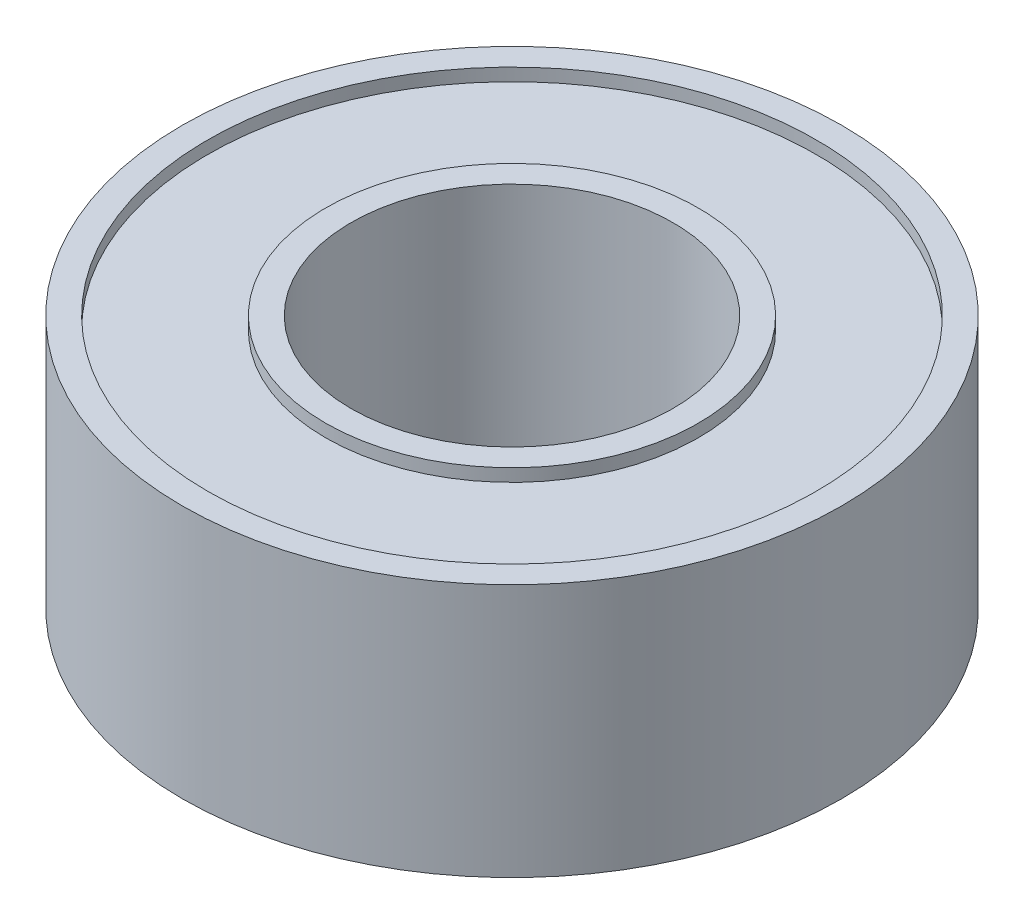
SolidWorks part; units mm, degrees
ref_plane "Front Plane" through (0, 0, 0) normal (0, 0, 1) x (1, 0, 0)
ref_plane "Top Plane" through (0, 0, 0) normal (0, 1, 0) x (1, 0, 0)
ref_plane "Right Plane" through (0, 0, 0) normal (1, 0, 0) x (0, 0, -1)
sketch "Sketch1" plane through (0, 0, 0) normal (0, 1, 0) x (1, 0, 0)
  circle A0 centre (0, 0) radius 3.175
  circle A1 centre (0, 0) radius 6.5
  dimension "D1" = 6.35
  dimension "D2" = 13
extrude "Boss-Extrude1" add sketch "Sketch1" along normal blind 5
ref_axis "Axis1" through (0, 5, 0) along (0, -1, 0)
sketch "Sketch2" plane through (0, 0, 0) normal (0, 0, 1) x (1, 0, 0)
  line L0 (6.5, 5) -> (-6.5, 5) construction
  line L1 (-6, 5) -> (-3.675, 5)
  line L2 (-6, 5) -> (-6, 4.75)
  line L3 (-6, 4.75) -> (-3.675, 4.75)
  line L4 (-3.675, 5) -> (-3.675, 4.75)
  line L5 (-6.5, 0) -> (6.5, 0) construction
  line L6 (-6, 0) -> (-3.675, 0)
  line L7 (-6, 0) -> (-6, 0.25)
  line L8 (-6, 0.25) -> (-3.675, 0.25)
  line L9 (-3.675, 0) -> (-3.675, 0.25)
  line L10 (-6.5, 5) -> (-6.5, 0) construction
  line L12 (-3.175, 5) -> (-3.175, 0) construction
  dimension "D1" = 0.25
  dimension "D2" = 0.5
  dimension "D3" = 0.5
revolve "Cut-Revolve1" cut sketch "Sketch2" angle 360 about axis through (0, 5, 0) along (0, -1, 0)
